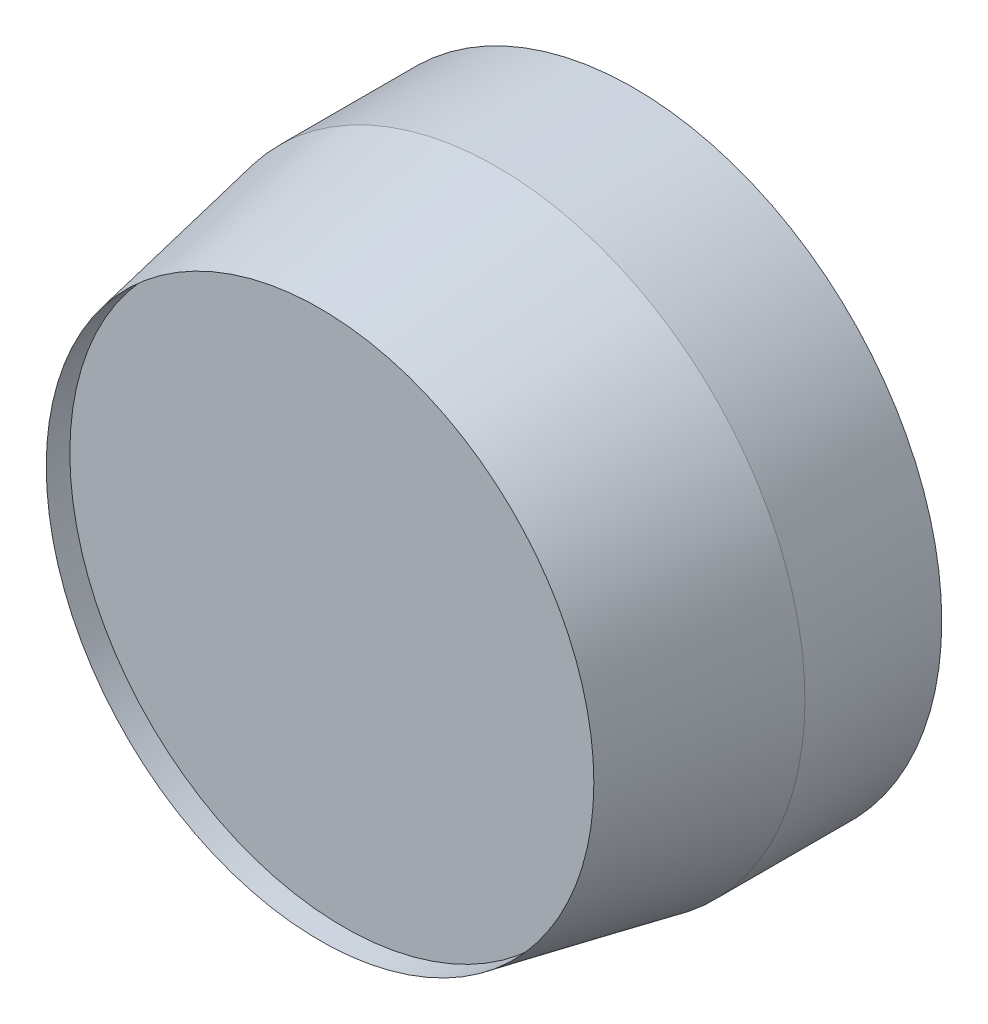
SolidWorks part; units mm, degrees
note: The reader was unsure of these and kept them because the rebuilt part matched: shared geometry of "Sketch1<3>".
ref_plane "Front Plane" through (0, 0, 0) normal (0, 0, 1) x (1, 0, 0)
ref_plane "Top Plane" through (0, 0, 0) normal (0, 1, 0) x (1, 0, 0)
ref_plane "Right Plane" through (0, 0, 0) normal (1, 0, 0) x (0, 0, -1)
sketch "Sketch1" plane through (0, 0, 0) normal (0, 0, 1) x (1, 0, 0)
  line L0 (-9.1703, 25.3261) -> (22.7072, 25.3261) construction
  circle A0 centre (-9.1703, 25.3261) radius 33.1678
  circle A1 centre (-9.1703, 25.3261) radius 31.8775
extrude "Boss-Extrude1" add sketch "Sketch1" against normal blind 14.732
ref_plane "Plane1" through (0, 0, 19.05) normal (0, 0, 1) x (1, 0, 0)
sketch "Sketch4" plane through (0, 0, 19.05) normal (0, 0, 1) x (1, 0, 0)
  circle A0 centre (-9.1703, 25.3261) radius 29.4845
loft "Loft1" add profiles "Sketch4" section "Sketch4" section "Sketch1<3>"
sketch "Sketch1<3>" plane through (0, 0, 0) normal (0, 0, 1) x (1, 0, 0) same geometry as "Sketch1"
sketch "Sketch5" plane through (0, 0, 19.05) normal (0, 0, 1) x (1, 0, 0)
  circle A0 centre (-9.1703, 25.3261) radius 29.4845
extrude "Cut-Extrude1" cut sketch "Sketch5" against normal blind 2.54
scale "Scale1" scale about centroid uniform scaling yes scale factor 13
